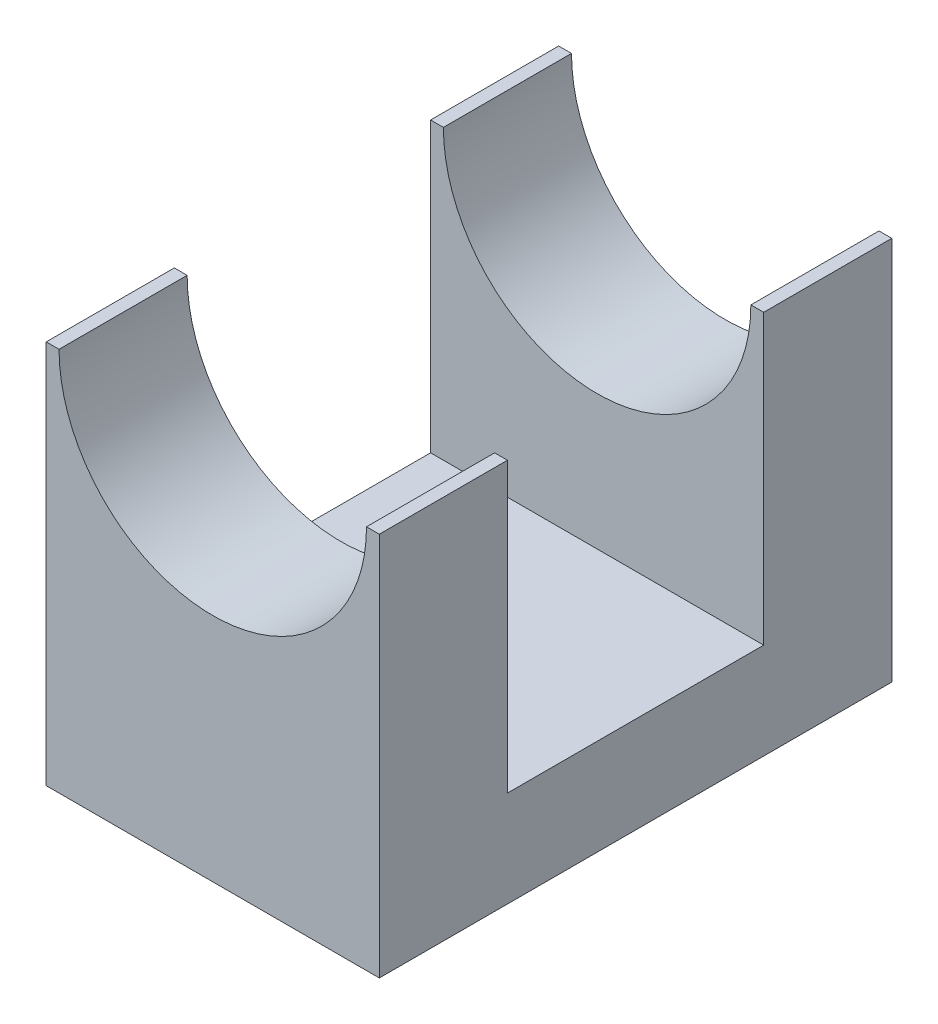
SolidWorks part; units mm, degrees
ref_plane "Front Plane" through (0, 0, 0) normal (0, 0, 1) x (1, 0, 0)
ref_plane "Top Plane" through (0, 0, 0) normal (0, 1, 0) x (1, 0, 0)
ref_plane "Right Plane" through (0, 0, 0) normal (1, 0, 0) x (0, 0, -1)
sketch "Sketch1" plane through (0, 0, 0) normal (0, 0, 1) x (1, 0, 0)
  line L0 (-52, 0) -> (-52, -120)
  line L1 (-52, -120) -> (52, -120)
  line L2 (52, -120) -> (52, 0)
  line L3 (-52, 0) -> (-48, 0)
  line L4 (48, 0) -> (52, 0)
  arc A1 (-48, 0) -> (48, 0) centre (0, 0) ccw
  point P4 (0, 0)
  point P9 (0, 0)
  dimension "D1" = 120
  dimension "D3" = 48
  dimension "D2" = 96
extrude "Boss-Extrude1" add sketch "Sketch1" along normal blind 40
sketch "Sketch2" plane through (0, 0, 0) normal (0, 0, -1) x (-1, 0, 0)
  line L0 (-52, -120) -> (-52, -90)
  line L1 (-52, -120) -> (-52, 0) construction
  line L2 (-52, -90) -> (52, -90)
  line L3 (52, 0) -> (52, -120) construction
  line L4 (52, -90) -> (52, -120)
  line L5 (52, -120) -> (-52, -120)
  dimension "D1" = 30
extrude "Boss-Extrude2" add sketch "Sketch2" along normal blind 80
extrude "Boss-Extrude3" add sketch "Sketch1<2>" against normal blind 40 from surface starting at face at (0, -105, -80)
sketch "Sketch1<2>" plane through (0, 0, 0) normal (0, 0, 1) x (1, 0, 0) same geometry as "Sketch1"
